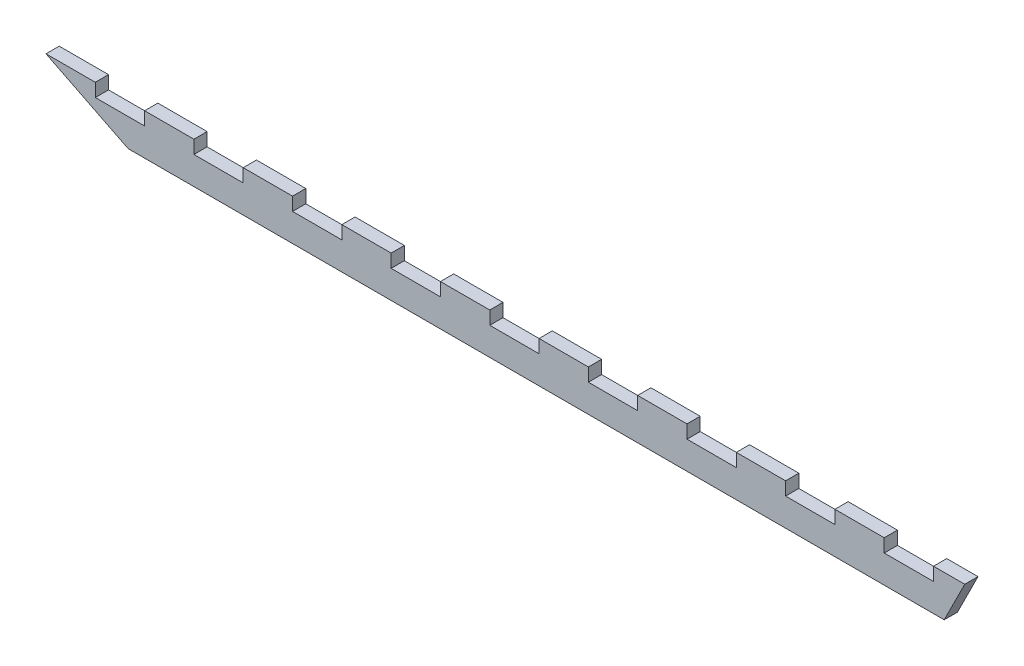
SolidWorks part; units mm, degrees
ref_plane "Front Plane" through (0, 0, 0) normal (0, 0, 1) x (1, 0, 0)
ref_plane "Top Plane" through (0, 0, 0) normal (0, 1, 0) x (1, 0, 0)
ref_plane "Right Plane" through (0, 0, 0) normal (1, 0, 0) x (0, 0, -1)
sketch "Sketch1" plane through (0, 0, 0) normal (0, 0, 1) x (1, 0, 0)
  line L0 (-95.7754, -4.7039) -> (-115.7754, 5.2961)
  line L3 (-95.7754, -4.7039) -> (102.8314, -4.7039)
  line L5 (-115.7754, 5.2961) -> (107.8314, 5.2961)
  line L6 (-95.7754, -4.7039) -> (107.8314, 5.2961) construction
  line L7 (102.8314, -4.7039) -> (107.8314, 5.2961)
  line L8 (102.8314, -4.7039) -> (-115.7754, 5.2961) construction
  point P0 (98.1261, -4.623)
  dimension "D1" = 26.565
  dimension "D2" = 223.6068
  dimension "D3" = 10
  dimension "D4" = 63.435
extrude "Boss-Extrude1" add sketch "Sketch1" along normal mid plane 3.22
sketch "Sketch2" plane through (0, 0, 1.61) normal (0, 0, 1) x (1, 0, 0)
  line L0 (107.8314, 5.2961) -> (-115.7754, 5.2961) construction
  line L1 (-103.7754, 5.2961) -> (-91.7754, 5.2961)
  line L2 (-103.7754, 5.2961) -> (-103.7754, 2.0761)
  line L3 (-103.7754, 2.0761) -> (-91.7754, 2.0761)
  line L4 (-91.7754, 5.2961) -> (-91.7754, 2.0761)
  line L5 (-115.7754, 5.2961) -> (-103.7754, 5.2961) construction
  dimension "D1" = 12
  dimension "D2" = 3.22
extrude "Cut-Extrude1" cut sketch "Sketch2" against normal up to next
pattern_linear "LPattern1" count 9 spacing 24 along (1, 0, 0) of "Cut-Extrude1"
equation "\"D1@Sketch1\"=atn(10/20)"
equation "\"D2@Sketch1\"=sqr(100^2+200^2)"
equation "\"D4@Sketch1\"=90-\"D1@Sketch1\""
equation "\"D3@LPattern1\"=2*\"D1@Sketch2\""
